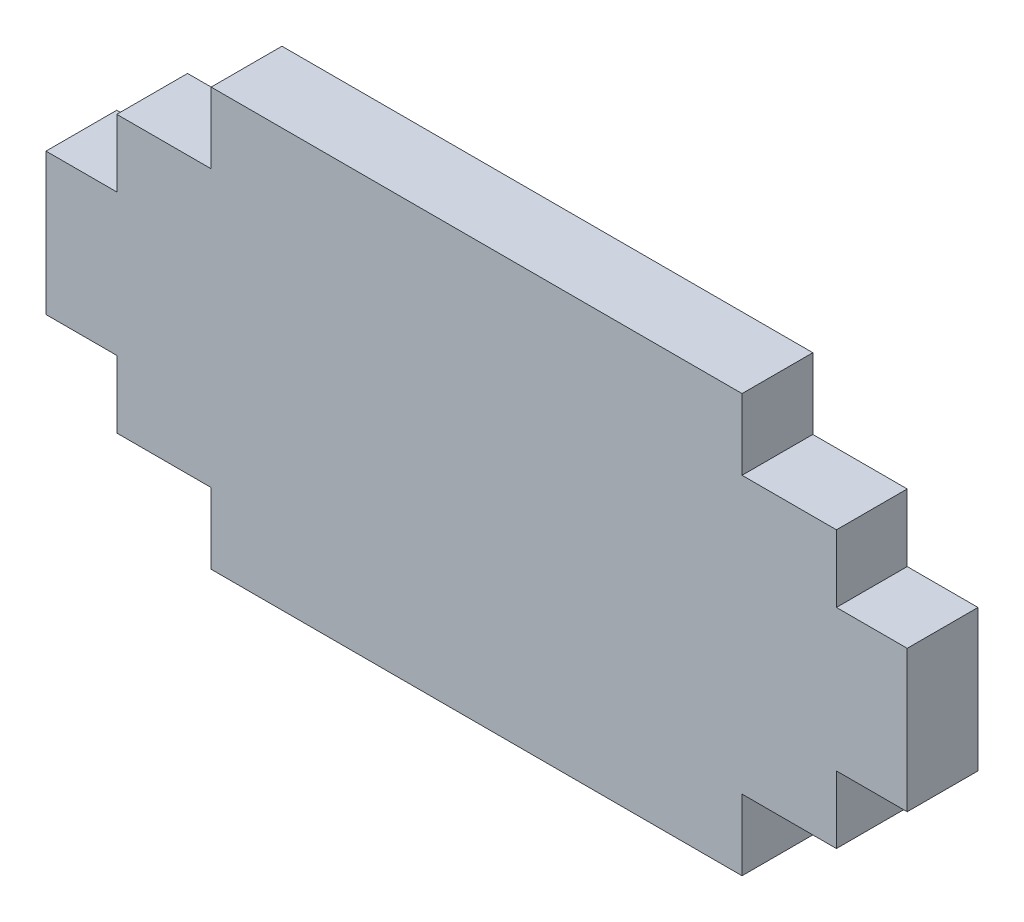
SolidWorks part; units mm, degrees
ref_plane "Ebene vorne (XY)" through (0, 0, 0) normal (0, 0, 1) x (1, 0, 0)
ref_plane "Ebene oben  (XZ)" through (0, 0, 0) normal (0, 1, 0) x (1, 0, 0)
ref_plane "Ebene rechts  (YZ)" through (0, 0, 0) normal (1, 0, 0) x (0, 0, -1)
ref_axis "x-Achse" through (-4.825, 0, 0) along (1, 0, 0)
ref_axis "y-Achse" through (0, 9.735, 0) along (0, -1, 0)
ref_axis "z-Achse" through (0, 0, -0.15) along (0, 0, 1)
sketch "Profile_Laser_profile_3mm" plane through (0, 0, 0) normal (0, 0, 1) x (1, 0, 0)
  line L0 (0, -5.85) -> (4, -5.85)
  line L1 (4, -5.85) -> (4, -8.85)
  line L2 (4, -8.85) -> (26.5, -8.85)
  line L3 (26.5, -8.85) -> (26.5, -5.85)
  line L4 (26.5, -5.85) -> (30.5, -5.85)
  line L5 (30.5, -5.85) -> (30.5, -3)
  line L6 (30.5, -3) -> (33.5, -3)
  line L7 (33.5, -3) -> (33.5, 3)
  line L8 (33.5, 3) -> (30.5, 3)
  line L9 (30.5, 3) -> (30.5, 5.85)
  line L10 (30.5, 5.85) -> (26.5, 5.85)
  line L11 (26.5, 5.85) -> (26.5, 8.85)
  line L12 (26.5, 8.85) -> (4, 8.85)
  line L13 (4, 8.85) -> (4, 5.85)
  line L14 (4, 5.85) -> (0, 5.85)
  line L15 (0, 5.85) -> (0, 3)
  line L16 (0, 3) -> (-3, 3)
  line L17 (-3, 3) -> (-3, -3)
  line L18 (-3, -3) -> (0, -3)
  line L19 (0, -3) -> (0, -5.85)
extrude "Laser_profile_3mm" add sketch "Profile_Laser_profile_3mm" along normal blind 3
